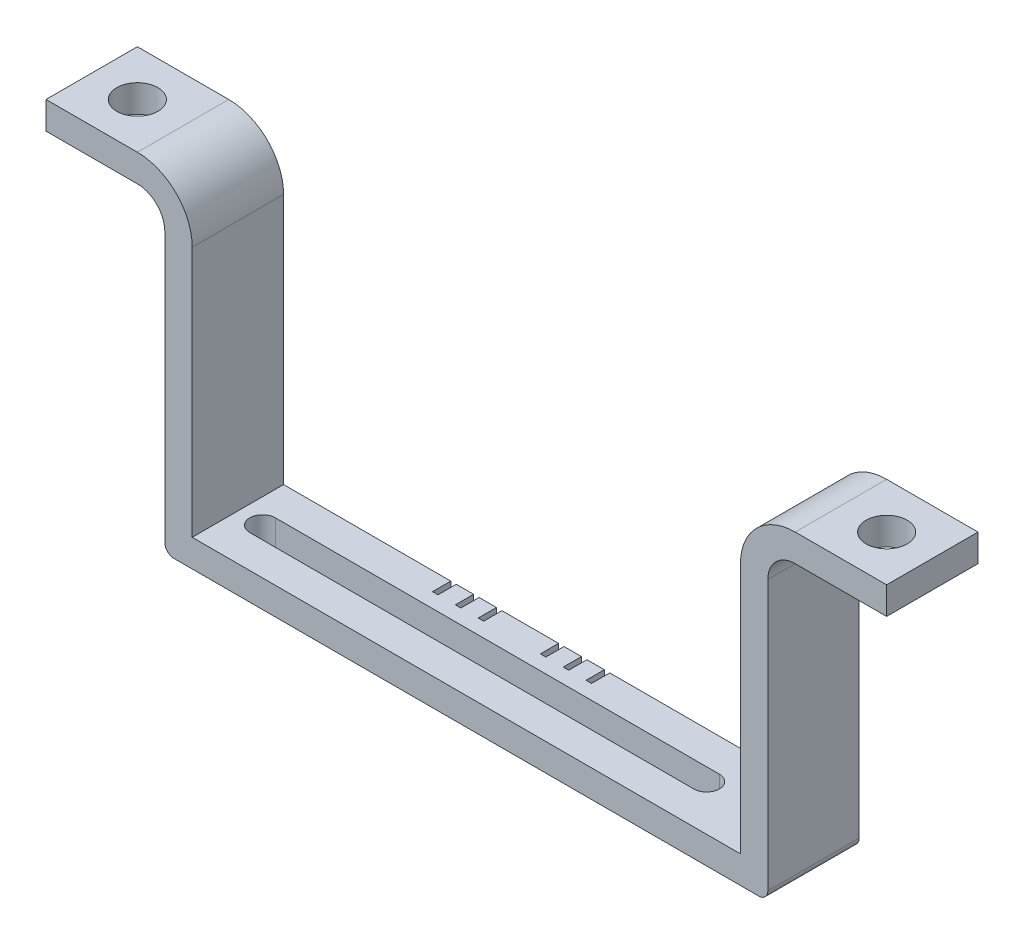
SolidWorks part; units mm, degrees
ref_plane "Front Plane" through (0, 0, 0) normal (0, 0, 1) x (1, 0, 0)
ref_plane "Top Plane" through (0, 0, 0) normal (0, 1, 0) x (1, 0, 0)
ref_plane "Right Plane" through (0, 0, 0) normal (1, 0, 0) x (0, 0, -1)
sketch "Sketch1" plane through (0, 0, 0) normal (0, 0, 1) x (1, 0, 0)
  line L0 (-46, 33.5) -> (-36, 33.5)
  line L1 (-30, 27.5) -> (-30, 0)
  line L2 (-30, 0) -> (30, 0)
  line L3 (30, 0) -> (30, 27.5)
  line L4 (36, 33.5) -> (46, 33.5)
  line L5 (-46, 30.5) -> (-36, 30.5)
  line L6 (-33, 27.5) -> (-33, -2)
  line L7 (-32, -3) -> (32, -3)
  line L8 (33, -2) -> (33, 27.5)
  line L9 (36, 30.5) -> (46, 30.5)
  line L10 (-46, 30.5) -> (-46, 33.5)
  line L11 (46, 33.5) -> (46, 30.5)
  line L12 (-30, 33.5) -> (-30, 0) construction
  line L13 (-46, 33.5) -> (-30, 33.5) construction
  line L14 (-33, 30.5) -> (-33, -3) construction
  line L15 (-46, 30.5) -> (-33, 30.5) construction
  line L16 (30, 0) -> (30, 33.5) construction
  line L17 (30, 33.5) -> (46, 33.5) construction
  line L18 (33, -3) -> (33, 30.5) construction
  line L19 (33, 30.5) -> (46, 30.5) construction
  line L20 (-33, -3) -> (33, -3) construction
  arc A0 (-30, 27.5) -> (-36, 33.5) centre (-36, 27.5) ccw
  arc A1 (-33, 27.5) -> (-36, 30.5) centre (-36, 27.5) ccw
  arc A2 (30, 27.5) -> (36, 33.5) centre (36, 27.5) cw
  arc A3 (33, 27.5) -> (36, 30.5) centre (36, 27.5) cw
  arc A4 (33, -2) -> (32, -3) centre (32, -2) cw
  arc A5 (-32, -3) -> (-33, -2) centre (-32, -2) cw
  point P6 (0, 0)
  dimension "D4" = 6
  dimension "D5" = 3
  dimension "D6" = 6
  dimension "D7" = 3
  dimension "D8" = 1
  dimension "D1" = 60
  dimension "D3" = 36.5
  dimension "D9" = 10
  dimension "D2" = 3
extrude "Boss-Extrude1" add sketch "Sketch1" along normal mid plane 10 contours L0 A0 L1 L2 L3 A2 L4 L11 L9 A3 L8 A4 L7 A5 L6 A1 L5 L10
sketch "Sketch3" plane through (0, 0, 0) normal (0, 1, 0) x (1, 0, 0)
  line L0 (-27.3, 0) -> (21.3, 0) construction
  line L1 (-27.3, 1.4) -> (21.3, 1.4)
  line L2 (-27.3, -1.4) -> (21.3, -1.4)
  line L3 (-30, -5) -> (-30, 5) construction
  line L4 (30, -5) -> (30, 5) construction
  arc A0 (-27.3, 1.4) -> (-27.3, -1.4) centre (-27.3, 0) ccw
  arc A1 (21.3, -1.4) -> (21.3, 1.4) centre (21.3, 0) ccw
  point P3 (-3, 0)
  point P10 (22.6416, 0)
  dimension "D1" = 2.8
  dimension "D2" = 8.7
  dimension "D3" = 2.7
extrude "Cut-Extrude1" cut sketch "Sketch3" against normal through all contours L2 A1 L1 A0
sketch "Sketch5" plane through (0, 33.5, 0) normal (0, 1, 0) x (1, 0, 0)
  line L0 (-46, 5) -> (-36, 5) construction
  line L1 (-46, -5) -> (-46, 5) construction
  line L2 (36, 5) -> (46, 5) construction
  circle A0 centre (-41, 0) radius 2.25
  circle A1 centre (41, 0) radius 2.25
  point P2 (0, 0)
  point P5 (-41, 5)
  point P8 (-46, 0)
  point P13 (41, 5)
  dimension "D1" = 4.5
extrude "Cut-Extrude2" cut sketch "Sketch5" against normal through all
sketch "Sketch6" plane through (0, 0, 0) normal (0, 1, 0) x (1, 0, 0)
  line L1 (-6.7, 5) -> (-6.1, 5)
  line L2 (-6.7, 5) -> (-6.7, 3)
  line L3 (-6.7, 3) -> (-6.1, 3)
  line L4 (-6.1, 5) -> (-6.1, 3)
  line L6 (-11.7, 5) -> (-11.1, 5)
  line L7 (0.1, 5) -> (0.7, 5)
  line L8 (0.1, 5) -> (0.1, 3)
  line L9 (0.1, 3) -> (0.7, 3)
  line L10 (0.7, 5) -> (0.7, 3)
  line L11 (-9.2, 5) -> (-8.6, 5)
  line L12 (-9.2, 5) -> (-9.2, 3)
  line L13 (-9.2, 3) -> (-8.6, 3)
  line L14 (-8.6, 5) -> (-8.6, 3)
  line L15 (2.6, 5) -> (3.2, 5)
  line L16 (2.6, 5) -> (2.6, 3)
  line L17 (2.6, 3) -> (3.2, 3)
  line L18 (3.2, 5) -> (3.2, 3)
  line L19 (-11.7, 5) -> (-11.7, 3)
  line L20 (-11.7, 3) -> (-11.1, 3)
  line L21 (-11.1, 5) -> (-11.1, 3)
  line L22 (-30, 5) -> (30, 5) construction
  line L23 (5.1, 5) -> (5.7, 5)
  line L24 (5.1, 5) -> (5.1, 3)
  line L25 (5.1, 3) -> (5.7, 3)
  line L26 (5.7, 5) -> (5.7, 3)
  point P4 (-6.4, 3)
  point P13 (0.4, 3)
  point P18 (-8.9, 3)
  point P23 (2.9, 3)
  point P28 (4.9, 2.043)
  point P29 (-11.4, 5)
  point P30 (5.4, 5)
  dimension "D1" = 6.4
  dimension "D3" = 2
  dimension "D4" = 0.6
  dimension "D5" = 6.8
  dimension "D6" = 8.9
  dimension "D7" = 11.8
  dimension "D8" = 11.4
  dimension "D9" = 16.8
extrude "Cut-Extrude3" cut sketch "Sketch6" against normal blind 0.6
